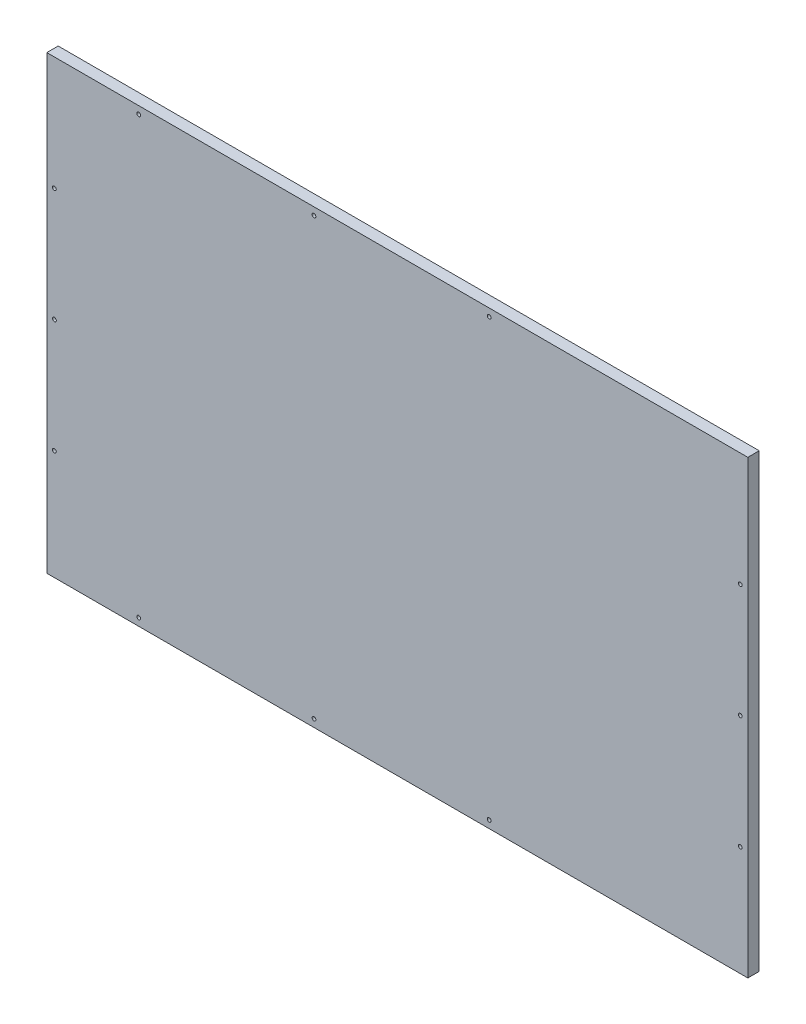
SolidWorks part; units mm, degrees
material "西洋杉"
ref_plane "正面" through (0, 0, 0) normal (0, 0, 1) x (1, 0, 0)
ref_plane "平面" through (0, 0, 0) normal (0, 1, 0) x (1, 0, 0)
ref_plane "右側面" through (0, 0, 0) normal (1, 0, 0) x (0, 0, -1)
sketch "ｽｹｯﾁ1" plane through (0, 0, 0) normal (0, 0, 1) x (1, 0, 0)
  line L1 (-462.5, 297.5) -> (462.5, 297.5)
  line L2 (-462.5, 297.5) -> (-462.5, -297.5)
  line L3 (-462.5, -297.5) -> (462.5, -297.5)
  line L4 (462.5, 297.5) -> (462.5, -297.5)
  line L5 (-462.5, 297.5) -> (462.5, -297.5) construction
  line L6 (-462.5, -297.5) -> (462.5, 297.5) construction
  point P0 (0, 0)
  dimension "D1" = 595
  dimension "D2" = 925
extrude "ﾎﾞｽ - 押し出し1" add sketch "ｽｹｯﾁ1" along normal blind 15
sketch "ｽｹｯﾁ2" plane through (0, 0, 15) normal (0, 0, 1) x (1, 0, 0)
  line L0 (-452.5, 297.5) -> (-452.5, -297.5) construction
  line L1 (462.5, 297.5) -> (-462.5, 297.5) construction
  line L2 (-462.5, -297.5) -> (462.5, -297.5) construction
  line L3 (-462.5, 297.5) -> (-462.5, -297.5) construction
  line L4 (-462.5, 287.5) -> (462.5, 287.5) construction
  line L5 (462.5, -297.5) -> (462.5, 297.5) construction
  circle A0 centre (-452.5, 147.5) radius 2.5
  circle A1 centre (-452.5, -2.5) radius 2.5
  circle A2 centre (-452.5, -152.5) radius 2.5
  circle A3 centre (-341.25, 287.5) radius 2.5
  circle A4 centre (-110, 287.5) radius 2.5
  circle A5 centre (121.25, 287.5) radius 2.5
  dimension "D2" = 5
  dimension "D7" = 5
  dimension "D1" = 10
  dimension "D3" = 150
  dimension "D5" = 10
  dimension "D6" = 925
  dimension "D8" = 121.25
  dimension "D10" = 595
  dimension "D11" = 150
  dimension "D4" = 3
  dimension "D9" = 3
extrude "ｶｯﾄ - 押し出し1" cut sketch "ｽｹｯﾁ2" against normal through all contours A3 | A4 | A5
extrude "ｶｯﾄ - 押し出し2" cut sketch "ｽｹｯﾁ2<3>" against normal through all contours A0 | A1 | A2
sketch "ｽｹｯﾁ2<3>" plane through (0, 0, 15) normal (0, 0, 1) x (1, 0, 0) same geometry as "ｽｹｯﾁ2"
mirror "ﾐﾗｰ1" about plane through (0, 0, 0) normal (0, 1, 0) of "ｶｯﾄ - 押し出し1"
mirror "ﾐﾗｰ2" about plane through (0, 0, 0) normal (1, 0, 0) of "ｶｯﾄ - 押し出し2"
equation "\"D8@ｽｹｯﾁ2\"=\"D6@ｽｹｯﾁ2\"/4"
